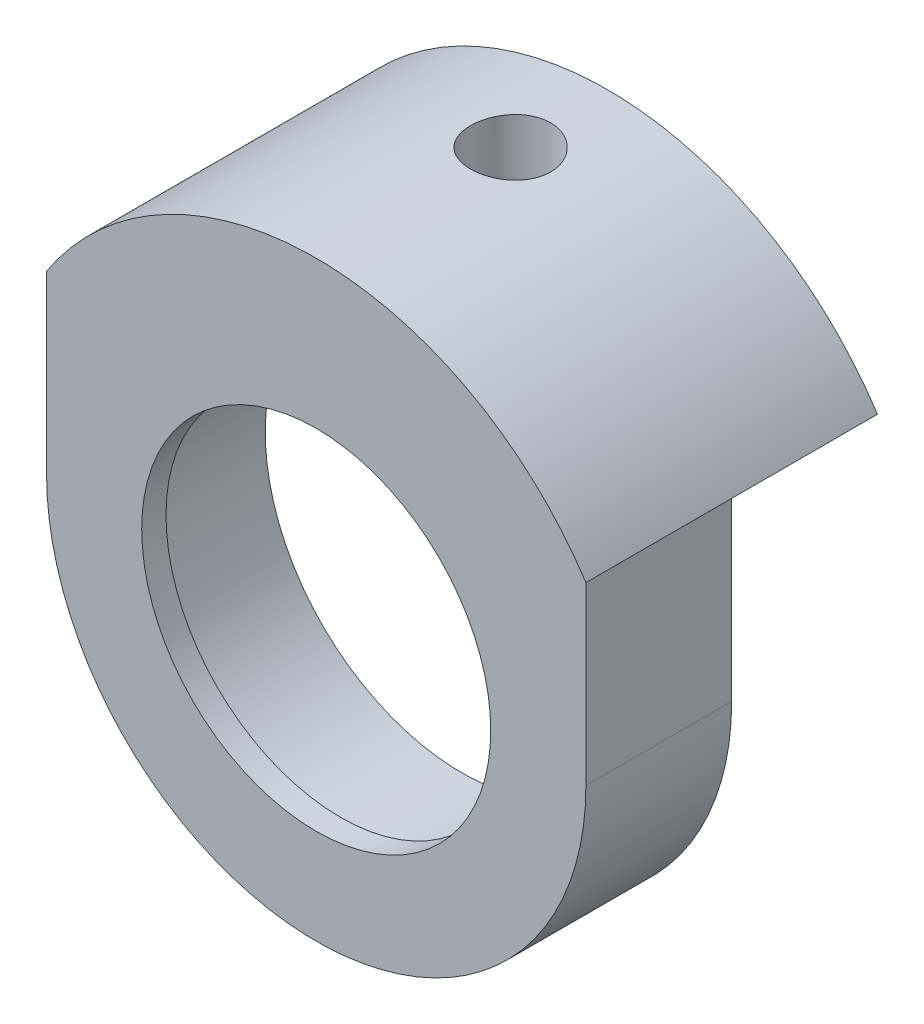
SolidWorks part; units mm, degrees
ref_plane "Front Plane" through (0, 0, 0) normal (0, 0, 1) x (1, 0, 0)
ref_plane "Top Plane" through (0, 0, 0) normal (0, 1, 0) x (1, 0, 0)
ref_plane "Right Plane" through (0, 0, 0) normal (1, 0, 0) x (0, 0, -1)
sketch "Sketch1" plane through (0, 0, 0) normal (0, 0, 1) x (1, 0, 0)
  line L0 (-11.1, 0) -> (11.1, 0)
  line L1 (-11.1, 0) -> (-11.1, 7.2355)
  line L2 (11.1, 0) -> (11.1, 7.2355)
  circle A0 centre (0, 0) radius 8.1
  circle A1 centre (0, 0) radius 13.25
  circle A2 centre (0, 0) radius 11.1
  dimension "16.2" = 16.2
  dimension "D2" = 26.5
  dimension "D3" = 3
extrude "Boss-Extrude1" add sketch "Sketch1" along normal blind 12 contours L0 A2 A0 | A2 L2 A1 L1 | L0 A2 A0 region at (0, 8.3482, 0) region at (9.6, -0.2482, 0) region at (0, 11.3585, 0)
sketch "Sketch2" plane through (-11.1, 0, 0) normal (-1, 0, 0) x (0, 0, 1)
  line L0 (12, 0) -> (12, 7.2355) construction
  line L1 (0, 7.2355) -> (6, 7.2355)
  line L2 (0, 7.2355) -> (0, -11.1)
  line L3 (0, -11.1) -> (6, -11.1)
  line L4 (6, 7.2355) -> (6, -11.1)
  dimension "D1" = 6
extrude "Cut-Extrude1" cut sketch "Sketch2" against normal up to surface (22.2 mm away) up to face at (11.1, 3.6178, 6)
sketch "Sketch3" plane through (0, 7.2355, 0) normal (0, -1, 0) x (1, 0, 0)
  line L0 (-3.6411, 0) -> (3.6411, 0) construction
  circle A0 centre (0, 4) radius 1.65
  dimension "D1" = 3.3
  dimension "D2" = 4
extrude "Cut-Extrude2" cut sketch "Sketch3" against normal up to surface (5.9114 mm away) up to face at (0, 9.2403, 6)
sketch "Sketch4" plane through (0, 7.2355, 0) normal (0, -1, 0) x (1, 0, 0)
  line L0 (-3.6411, 0) -> (3.6411, 0) construction
  line L1 (1.6166, 6.8) -> (-1.6166, 6.8)
  line L2 (-1.6166, 6.8) -> (-3.2332, 4)
  line L3 (-3.2332, 4) -> (-1.6166, 1.2)
  line L4 (-1.6166, 1.2) -> (1.6166, 1.2)
  line L5 (1.6166, 1.2) -> (3.2332, 4)
  line L6 (3.2332, 4) -> (1.6166, 6.8)
  circle A0 centre (0, 4) radius 2.8 construction
  dimension "D1" = 5.6
extrude "Cut-Extrude3" cut sketch "Sketch4" against normal blind 3
sketch "Sketch5" plane through (0, 0, 12) normal (0, 0, 1) x (1, 0, 0)
  circle A0 centre (0, 0) radius 8.1835
  circle A1 centre (0, 0) radius 7.1835
  dimension "D1" = 1
extrude "Boss-Extrude2" add sketch "Sketch5" against normal blind 1
